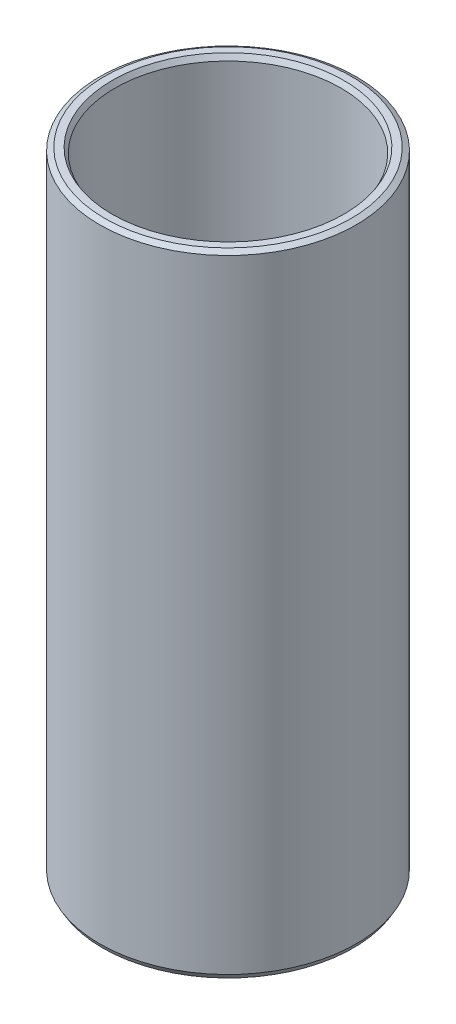
SolidWorks part; units mm, degrees
ref_plane "Front Plane" through (0, 0, 0) normal (0, 0, 1) x (1, 0, 0)
ref_plane "Top Plane" through (0, 0, 0) normal (0, 1, 0) x (1, 0, 0)
ref_plane "Right Plane" through (0, 0, 0) normal (1, 0, 0) x (0, 0, -1)
sketch "Sketch1" plane through (0, 0, 0) normal (0, 1, 0) x (1, 0, 0)
  circle A0 centre (0, 0) radius 47.5
  dimension "SLEEVE_OD" = 95
extrude "Boss-Extrude1" add sketch "Sketch1" along normal blind 233.4912
sketch "Sketch2" plane through (0, 0, 0) normal (0, 1, 0) x (1, 0, 0)
  circle A0 centre (0, 0) radius 41.8164
  dimension "BORE_D" = 83.6329
extrude "Cut-Extrude1" cut sketch "Sketch2" along normal through all
chamfer "Chamfer1" distance 1.0938 angle 60 4 edges at (0, 233.4912, 41.8164) (0, 0, 41.8164) (0, 0, 47.5) (0, 233.4912, 47.5) first distance on face at (0, 233.4912, 41.8164) first distance on face at (0, 0, 41.8164) first distance on face at (0, 233.4912, 47.5)
